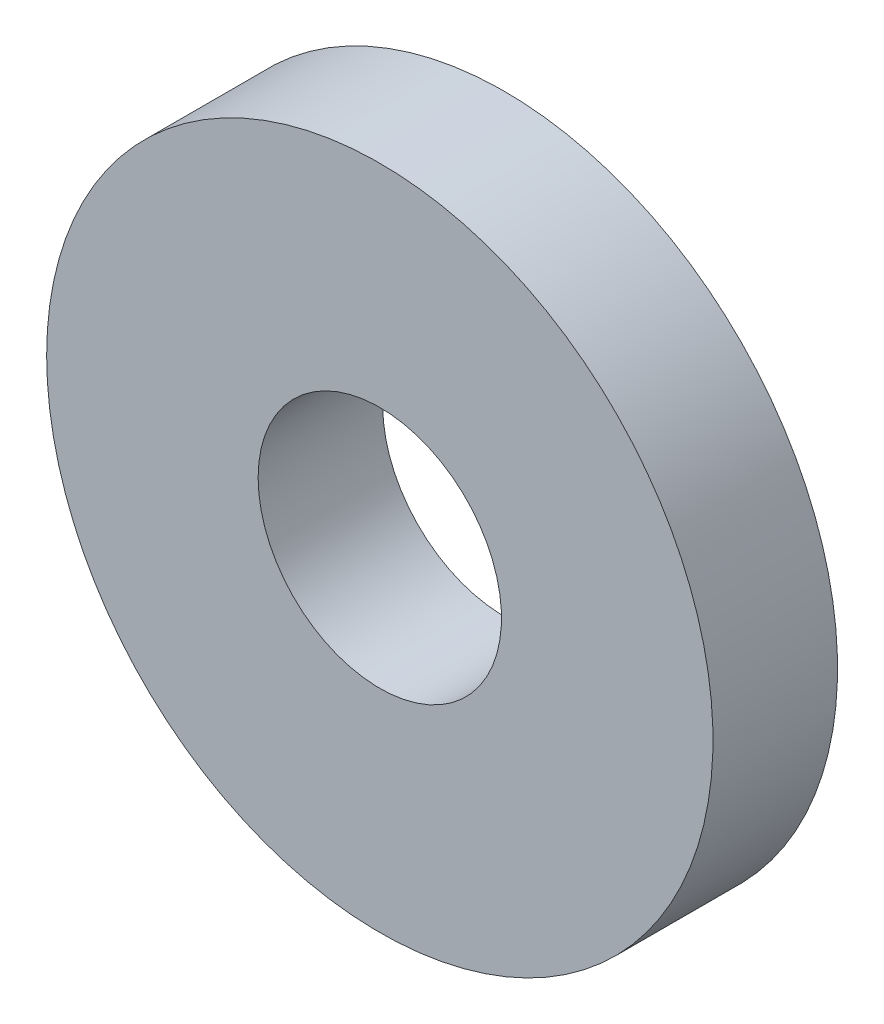
SolidWorks part; units mm, degrees
ref_plane "Front Plane" through (0, 0, 0) normal (0, 0, 1) x (1, 0, 0)
ref_plane "Top Plane" through (0, 0, 0) normal (0, 1, 0) x (1, 0, 0)
ref_plane "Right Plane" through (0, 0, 0) normal (1, 0, 0) x (0, 0, -1)
sketch "Sketch1" plane through (0, 0, 0) normal (0, 0, 1) x (1, 0, 0)
  circle A0 centre (0, 0) radius 11.5
  circle A1 centre (0, 0) radius 4.2
  dimension "OD" = 23
  dimension "ID1" = 8.4
extrude "Boss-Extrude1" add sketch "Sketch1" along normal blind 4.3
ref_axis "Center Axis 1" through (0, 0, 4.3) along (0, 0, -1)
ref_plane "Contact Plane 1" through (0, 0, 4.3) normal (0, 0, 1) x (1, 0, 0)
ref_plane "Contact Plane 2" through (0, 0, 0) normal (0, 0, -1) x (-1, 0, 0)
